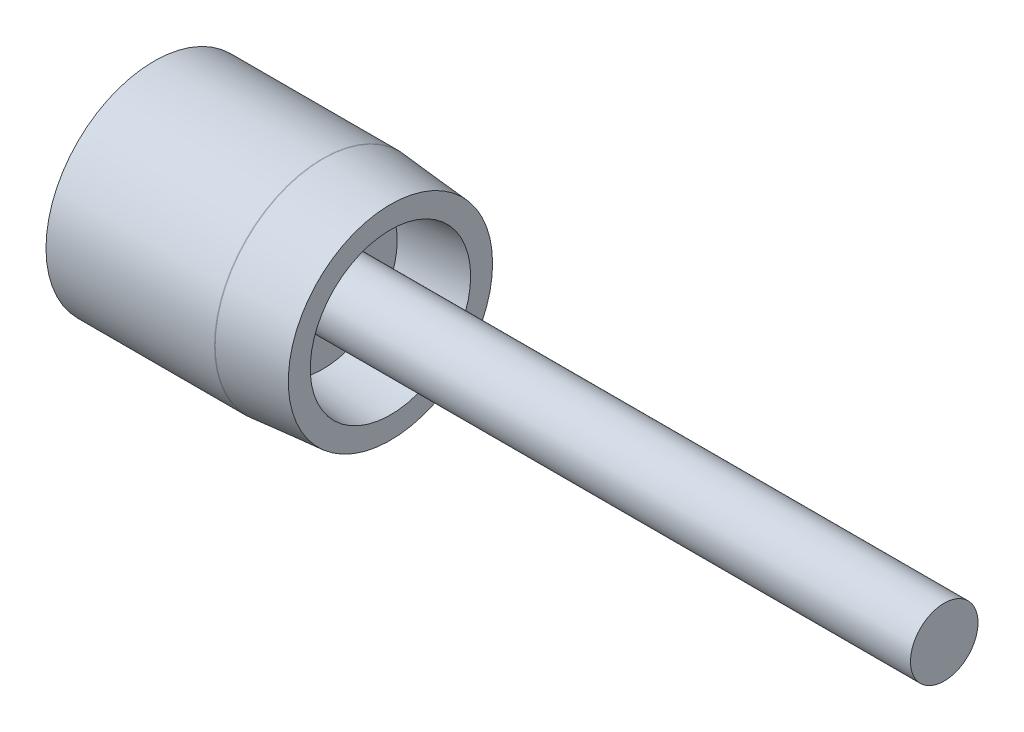
SolidWorks part; units mm, degrees
ref_plane "前视基准面" through (0, 0, 0) normal (0, 0, 1) x (1, 0, 0)
ref_plane "上视基准面" through (0, 0, 0) normal (0, 1, 0) x (1, 0, 0)
ref_plane "右视基准面" through (0, 0, 0) normal (1, 0, 0) x (0, 0, -1)
sketch "草图2" plane through (-136.0958, 0, 0) normal (1, 0, 0) x (0, 0, -1)
  circle A0 centre (-537.7618, -181.3143) radius 5
extrude "凸台-拉伸1" add sketch "草图2" against normal blind 92
sketch "草图3" plane through (-228.0958, 0, 0) normal (-1, 0, 0) x (0, 0, 1)
  circle A0 centre (537.7618, -181.3143) radius 16
extrude "凸台-拉伸2" add sketch "草图3" along normal blind 25
sketch "草图4" plane through (-228.0958, 0, 0) normal (1, 0, 0) x (0, 0, -1)
  circle A0 centre (-537.7618, -181.3143) radius 16
  circle A1 centre (-537.7618, -181.3143) radius 11
extrude "凸台-拉伸3" add sketch "草图4" along normal blind 10 draft 5
fillet "圆角1" radius 1 1 edges at (-228.0958, -181.3143, 521.7618)
